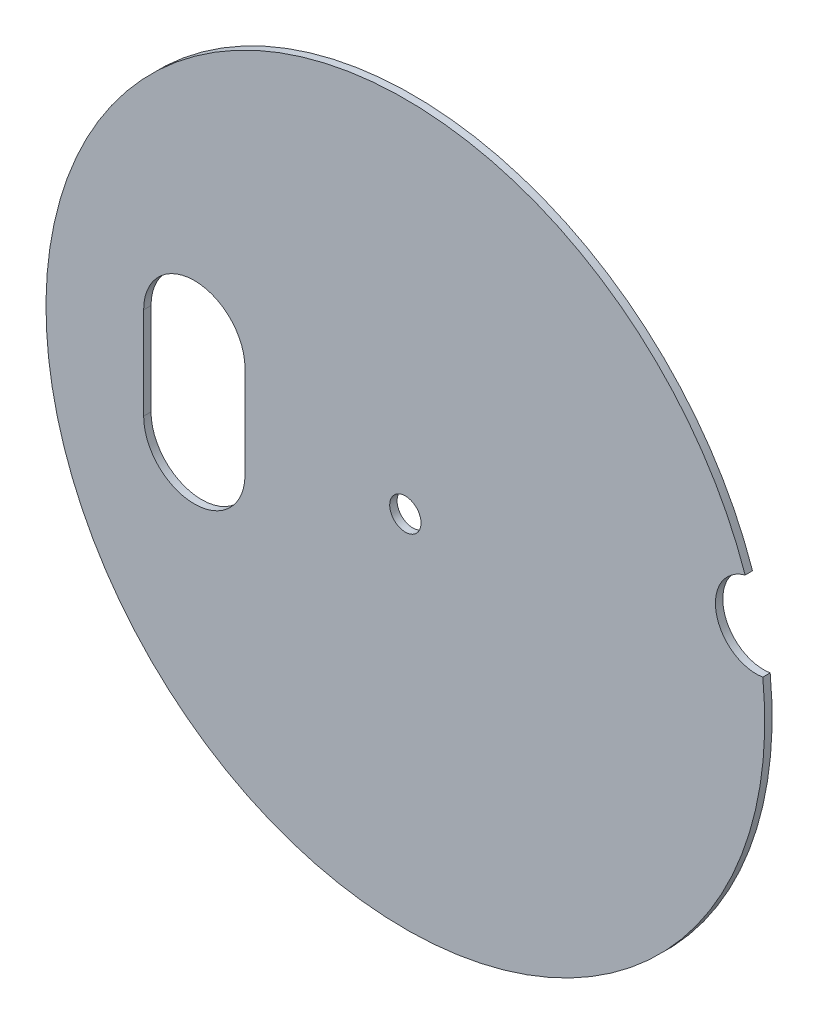
SolidWorks part; units mm, degrees
ref_plane "Plan de face" through (0, 0, 0) normal (0, 0, 1) x (1, 0, 0)
ref_plane "Plan de dessus" through (0, 0, 0) normal (0, 1, 0) x (1, 0, 0)
ref_plane "Plan de droite" through (0, 0, 0) normal (1, 0, 0) x (0, 0, -1)
sketch "Esquisse1" plane through (0, 0, 0) normal (0, 0, 1) x (1, 0, 0)
  line L0 (0, 0) -> (19.5, 0) construction
  line L1 (0, 19.5) -> (0, 0) construction
  line L2 (-6.7, -3.3481) -> (-6.7, 3.3481) construction
  line L3 (-11.45, -2.5) -> (-11.45, 2.5) construction
  line L4 (-14.2, -2.5) -> (-14.2, 2.5)
  line L5 (-8.7, -2.5) -> (-8.7, 2.5)
  line L6 (-11.45, 0) -> (0, 0) construction
  line L7 (0, 0) -> (19.0378, 4.2206) construction
  arc A0 (18.4362, 6.3528) -> (19.3936, 2.0339) centre (0, 0) ccw
  circle A4 centre (0, 0) radius 0.85
  arc A5 (18.4362, 6.3528) -> (19.3936, 2.0339) centre (19.0378, 4.2206) ccw
  arc A6 (-14.2, -2.5) -> (-8.7, -2.5) centre (-11.45, -2.5) ccw
  arc A7 (-8.7, 2.5) -> (-14.2, 2.5) centre (-11.45, 2.5) ccw
  point P5 (8.234, -1.9)
  point P6 (-7.9, -3)
  point P11 (-11.45, 0)
  point P20 (-11.45, 0)
  dimension "D1" = 39
  dimension "D10" = 1.7
  dimension "D2" = 1.9
  dimension "D3" = 3
  dimension "D4" = 7.9
  dimension "D5" = 8.234
  dimension "D6" = 5.5
  dimension "D11" = 2
  dimension "D9" = 12.5
  dimension "D13" = 19.5
  dimension "D7" = 5
extrude "Boss.-Extru.1" add sketch "Esquisse1" along normal blind 0.4
equation "\"D13@Esquisse1\"=\"D1@Esquisse1\"/2"
